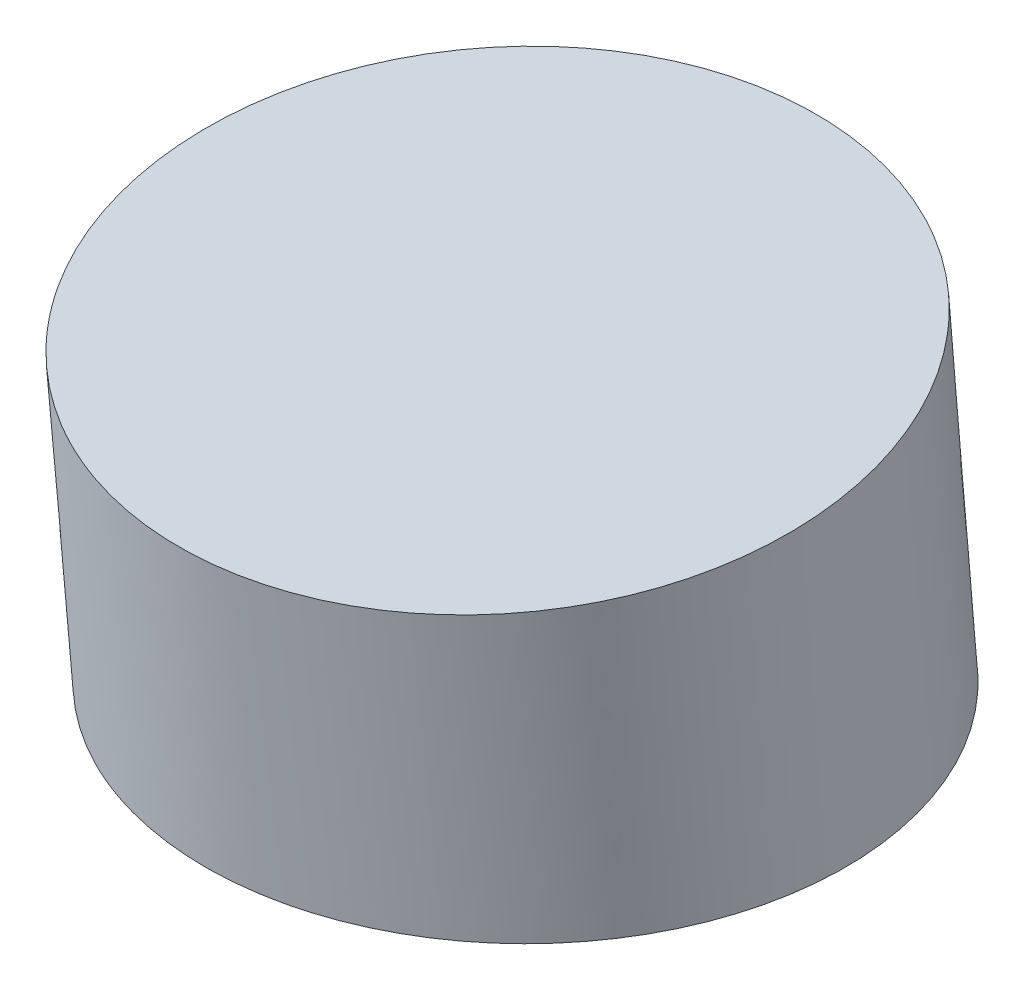
SolidWorks part; units mm, degrees
ref_plane "Front Plane" through (0, 0, 0) normal (0, 0, 1) x (1, 0, 0)
ref_plane "Top Plane" through (0, 0, 0) normal (0, 1, 0) x (1, 0, 0)
ref_plane "Right Plane" through (0, 0, 0) normal (1, 0, 0) x (0, 0, -1)
sketch "Sketch1" plane through (0, 0, 0) normal (0, 1, 0) x (1, 0, 0)
  line L0 (-5.5235, 0) -> (5.5235, 0) construction
  line L1 (-6.0759, 0) -> (6.0759, 0) construction
  circle A0 centre (0, 0) radius 5
  point P9 (0, 0)
  dimension "D1" = 10
ref_plane "Plane1" through (0, 0, 0) normal (0, 0.9962, 0.0872) x (1, 0, 0)
ref_plane "Plane2" through (0, 4.981, 0.4358) normal (0, 0.9962, 0.0872) x (1, 0, 0)
sketch "Sketch2" plane through (0, 4.981, 0.4358) normal (0, 0.9962, 0.0872) x (1, 0, 0)
  circle A0 centre (0, 0) radius 5
loft "Loft1" add profiles "Sketch1", "Sketch2" connector at (2.8802, 0, -4.0871) connector at (3.0893, 5.3236, -3.4807)
